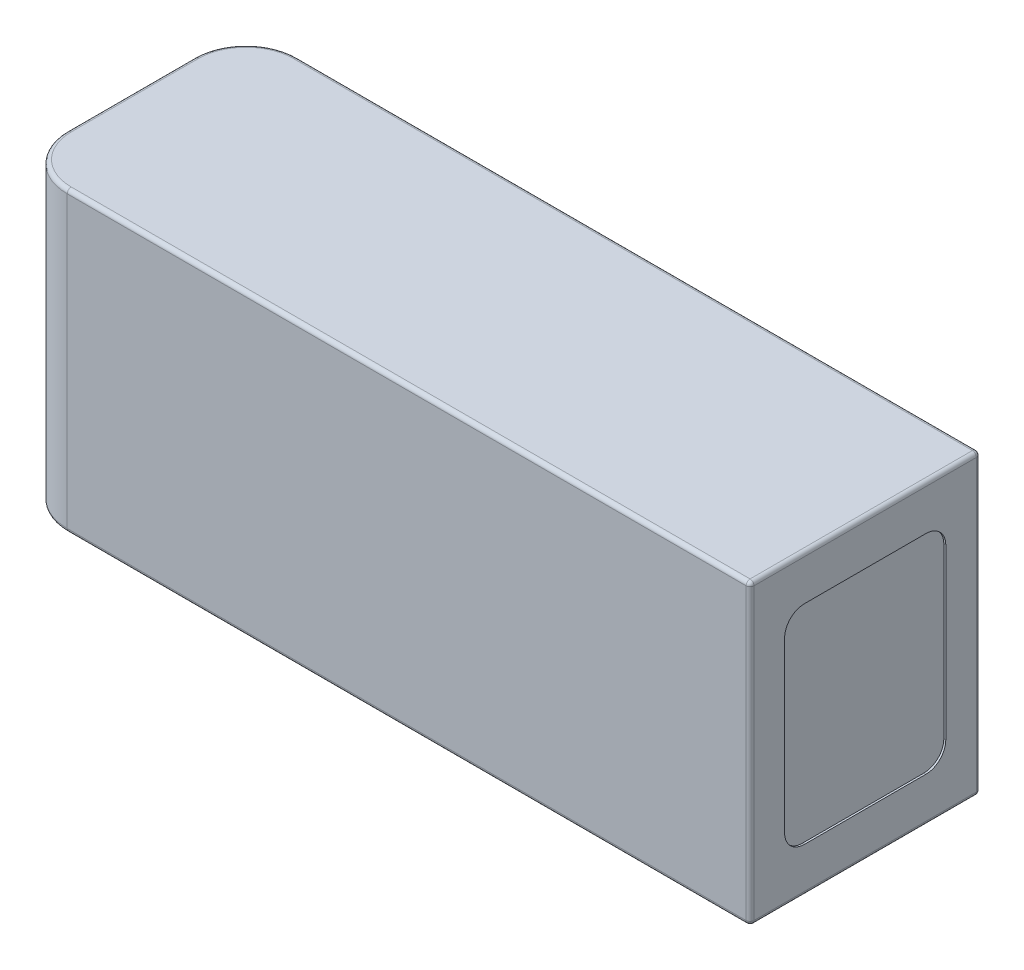
SolidWorks part; units mm, degrees
ref_plane "Front Plane" through (0, 0, 0) normal (0, 0, 1) x (1, 0, 0)
ref_plane "Top Plane" through (0, 0, 0) normal (0, 1, 0) x (1, 0, 0)
ref_plane "Right Plane" through (0, 0, 0) normal (1, 0, 0) x (0, 0, -1)
ref_plane "Plane1" through (0, 0, -15) normal (0, 0, -1) x (-1, 0, 0)
sketch "Sketch1" plane through (0, 0, -15) normal (0, 0, -1) x (-1, 0, 0)
  line L0 (-69, -22) -> (116, -22)
  line L1 (116, -22) -> (116, 53)
  line L2 (116, 53) -> (-69, 53)
  line L3 (-69, 53) -> (-69, -22)
  line L4 (-69, 15.5) -> (116, 15.5) construction
  line L5 (23.5, 53) -> (23.5, -22) construction
  dimension "D1" = 75
  dimension "D2" = 185
extrude "Boss-Extrude1" add sketch "Sketch1" against normal blind 58
sketch "Sketch2" plane through (69, 0, 0) normal (1, 0, 0) x (0, 0, -1)
  line L0 (-34.3, 36.75) -> (-34.3, -5.75)
  line L1 (-29.3, -10.75) -> (1.3, -10.75)
  line L2 (6.3, -5.75) -> (6.3, 36.75)
  line L3 (1.3, 41.75) -> (-29.3, 41.75)
  line L4 (-43, 53) -> (15, -22) construction
  line L5 (15, 53) -> (-43, -22) construction
  line L6 (-34.3, 41.75) -> (6.3, -10.75) construction
  line L7 (6.3, 41.75) -> (-34.3, -10.75) construction
  line L12 (-43, 53) -> (15, 53) construction
  line L13 (-43, 53) -> (-43, -22) construction
  line L14 (-43, -22) -> (15, -22) construction
  line L15 (15, 53) -> (15, -22) construction
  line L16 (-43, 53) -> (15, -22) construction
  line L17 (-43, -22) -> (15, 53) construction
  arc A0 (-34.3, -5.75) -> (-29.3, -10.75) centre (-29.3, -5.75) ccw
  arc A1 (1.3, -10.75) -> (6.3, -5.75) centre (1.3, -5.75) ccw
  arc A2 (6.3, 36.75) -> (1.3, 41.75) centre (1.3, 36.75) ccw
  arc A3 (-34.3, 36.75) -> (-29.3, 41.75) centre (-29.3, 36.75) cw
  point P16 (-14, 15.5)
  dimension "D2" = 58
  dimension "D3" = 5
  dimension "D1" = 40.6
extrude "Cut-Extrude1" cut sketch "Sketch2" against normal blind 0.5
sketch "Sketch3" plane through (-116, 0, 0) normal (-1, 0, 0) x (0, 0, 1)
  line L0 (27.75, 43.625) -> (0.25, 43.625)
  line L1 (-7.75, 35.625) -> (-7.75, -4.625)
  line L2 (0.25, -12.625) -> (27.75, -12.625)
  line L3 (35.75, -4.625) -> (35.75, 35.625)
  line L4 (-7.75, 43.625) -> (35.75, -12.625) construction
  line L5 (35.75, 43.625) -> (-7.75, -12.625) construction
  line L6 (-15, 53) -> (43, -22) construction
  line L7 (43, -22) -> (-15, -22) construction
  line L8 (-15, -22) -> (43, 53) construction
  arc A0 (-7.75, -4.625) -> (0.25, -12.625) centre (0.25, -4.625) ccw
  arc A1 (27.75, -12.625) -> (35.75, -4.625) centre (27.75, -4.625) ccw
  arc A2 (27.75, 43.625) -> (35.75, 35.625) centre (27.75, 35.625) cw
  arc A3 (0.25, 43.625) -> (-7.75, 35.625) centre (0.25, 35.625) ccw
  dimension "D3" = 8
  dimension "D1" = 43.5
  dimension "D2" = 58
extrude "Cut-Extrude2" cut sketch "Sketch3" against normal blind 0.5
fillet "Fillet1" radius 13 2 edges at (-116, 15.5, -15) (-116, 15.5, 43)
fillet "Fillet2" radius 1 14 edges at (69, 53, 14) (-17, 53, -15) (-112.1924, 53, -11.1924) (-17, 53, 43) (-116, 53, 14) (-112.1924, 53, 39.1924) (-116, -22, 14) (-112.1924, -22, -11.1924) (-112.1924, -22, 39.1924) (-17, -22, -15) (-17, -22, 43) (69, -22, 14) (69, 15.5, -15) (69, 15.5, 43)
sketch "Sketch4" [suppressed] plane through (0, 0, 10) normal (0, 0, 1) x (1, 0, 0)
  line L0 (-75, 4) -> (65, 4) construction
  line L1 (-75, 29) -> (-75, -21) construction
  line L2 (65, -21) -> (65, 29) construction
  line L3 (-5, 25.9735) -> (-5, -21) construction
  line L4 (-75, -21) -> (65, -21) construction
  circle A0 centre (-5, 4) radius 0.5026
sketch "Sketch5" plane through (68.5, 0, 0) normal (1, 0, 0) x (0, 0, -1)
  line L0 (-9, 49) -> (-19, 49) construction
  line L1 (-14, 53) -> (-14, 49) construction
  line L2 (-42, 53) -> (14, 53) construction
  circle A0 centre (-19, 49) radius 2
  circle A1 centre (-9, 49) radius 2
  dimension "D1" = 4
  dimension "D2" = 10
  dimension "D3" = 4
equation "\"D1@Sketch3\"=\"D2@Sketch3\" * .75"
equation "\"D1@Sketch2\"=\"D2@Sketch2\"* .7"
